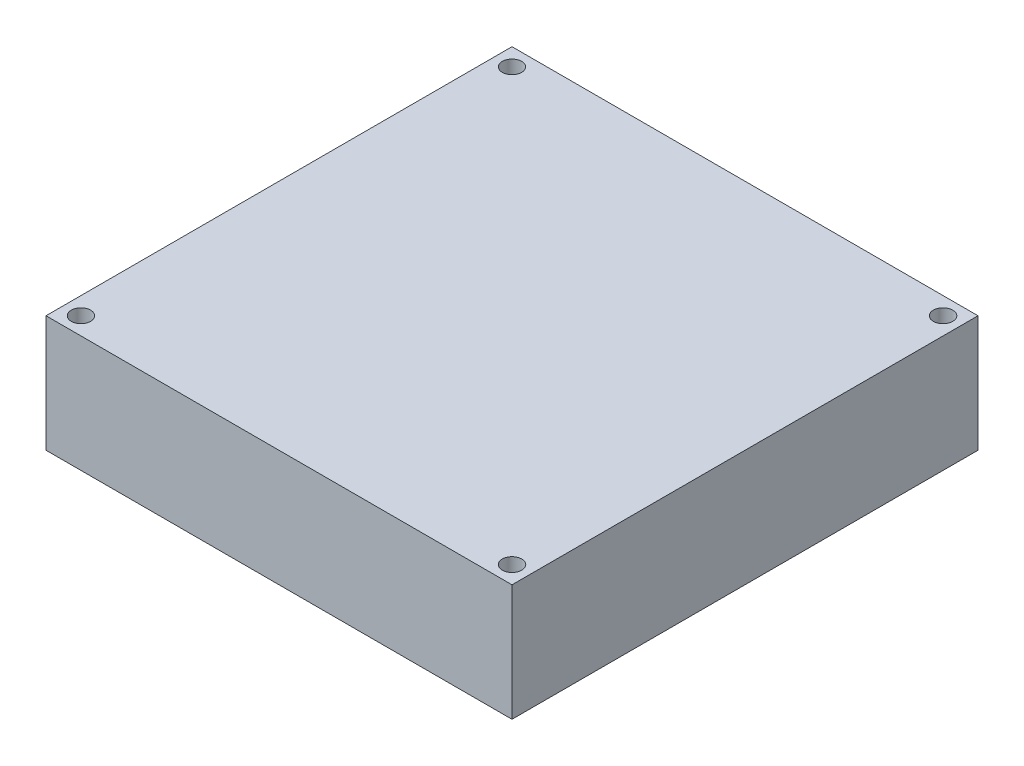
SolidWorks part; units mm, degrees
ref_plane "Front Plane" through (0, 0, 0) normal (0, 0, 1) x (1, 0, 0)
ref_plane "Top Plane" through (0, 0, 0) normal (0, 1, 0) x (1, 0, 0)
ref_plane "Right Plane" through (0, 0, 0) normal (1, 0, 0) x (0, 0, -1)
sketch "Sketch1" plane through (0, 0, 0) normal (0, 1, 0) x (1, 0, 0)
  line L1 (0, 0) -> (-60, 0)
  line L2 (0, 0) -> (0, 60)
  line L3 (0, 60) -> (-60, 60)
  line L4 (-60, 0) -> (-60, 60)
  dimension "D1" = 60
  dimension "D2" = 60
extrude "Boss-Extrude1" add sketch "Sketch1" along normal blind 15
sketch "Sketch2" plane through (0, 15, 0) normal (0, 1, 0) x (1, 0, 0)
  text T0 "H-Bridge" font "Century Gothic" height in points 16
sketch "Sketch3" plane through (0, 15, 0) normal (0, 1, 0) x (1, 0, 0)
  line L0 (-60, 60) -> (-57.75, 60)
  line L1 (0, 60) -> (-60, 60) construction
  line L2 (-60, 60) -> (-60, 57.75)
  line L3 (-60, 60) -> (-60, 0) construction
  line L4 (-60, 0) -> (-60, 2.25)
  line L6 (-60, 0) -> (0, 0) construction
  line L8 (0, 0) -> (0, 2.25)
  line L9 (0, 0) -> (0, 60) construction
  line L10 (0, 60) -> (-2.25, 60)
  line L11 (0, 60) -> (0, 57.75)
  line L16 (0, 0) -> (-2.25, 0)
  line L17 (-60, 0) -> (-57.75, 0)
  line L18 (-60, 57.75) -> (0, 57.75)
  line L19 (-2.25, 60) -> (-2.25, 0)
  line L20 (0, 2.25) -> (-60, 2.25)
  line L21 (-57.75, 0) -> (-57.75, 60)
  circle A0 centre (-57.75, 57.75) radius 1.2379
  circle A1 centre (-2.25, 57.75) radius 1.2525
  circle A2 centre (-2.25, 2.25) radius 1.2536
  circle A3 centre (-57.75, 2.25) radius 1.2482
  dimension "D1" = 2.25
  dimension "D2" = 2.25
  dimension "D3" = 2.25
  dimension "D5" = 2.25
  dimension "D6" = 2.25
  dimension "D4" = 2.25
extrude "Cut-Extrude1" cut sketch "Sketch3" against normal through all contours L20 A3 L21 | L21 A3 L20 | L20 A3 L21 | L21 A3 L20 | L21 A0 L18 | L18 A0 L21 | L21 A0 L18 | L18 A0 L21 | L19 A2 L20 | L20 A2 L19 | L19 A2 L20 | L20 A2 L19 | A1 region at (-57.2246, 15, -58.2754) region at (-58.2754, 15, -58.2754) region at (-58.2754, 15, -57.2246) region at (-57.2246, 15, -57.2246) region at (-57.2202, 15, -2.7798) region at (-58.2798, 15, -2.7798) region at (-58.2798, 15, -1.7202) region at (-57.2202, 15, -1.7202) region at (-1.7179, 15, -2.7821) region at (-2.7821, 15, -2.7821) region at (-2.7821, 15, -1.7179) region at (-1.7179, 15, -1.7179)
equation "\"D3@Sketch3\"=2.25mm"
